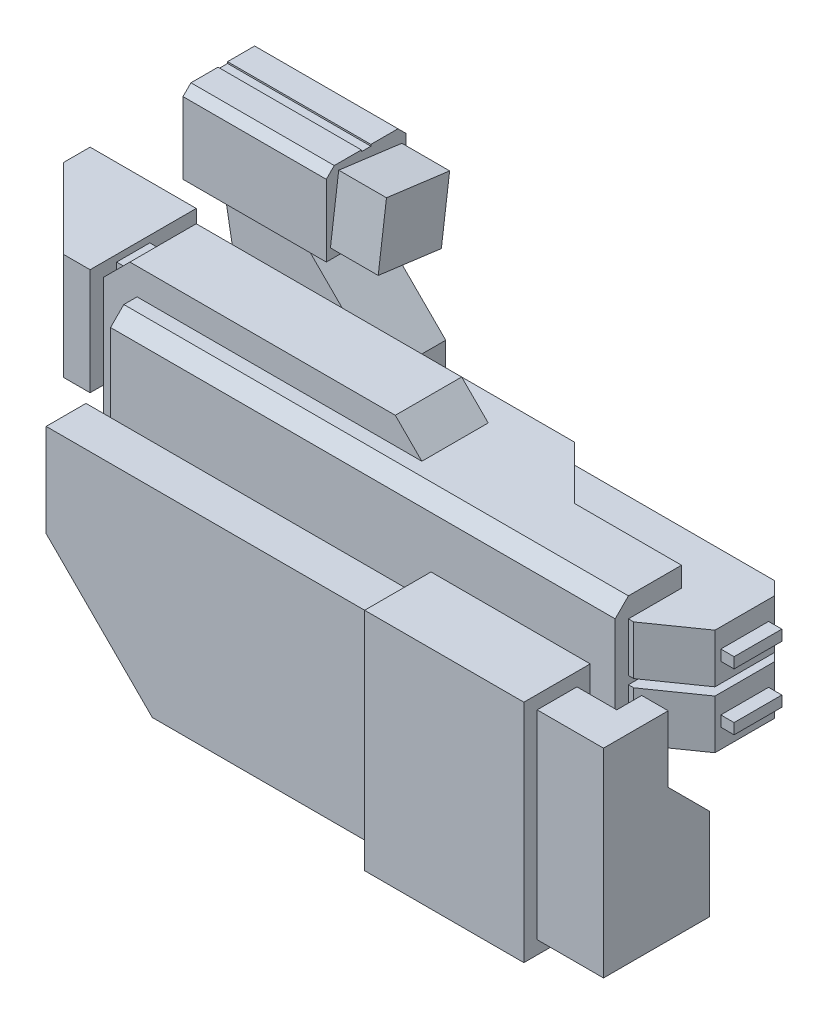
SolidWorks part; units mm, degrees
ref_plane "Front Plane" through (0, 0, 0) normal (0, 0, 1) x (1, 0, 0)
ref_plane "Top Plane" through (0, 0, 0) normal (0, 1, 0) x (1, 0, 0)
ref_plane "Right Plane" through (0, 0, 0) normal (1, 0, 0) x (0, 0, -1)
sketch "Sketch1" plane through (0, 0, 0) normal (0, 0, 1) x (1, 0, 0)
  line L0 (0, 0) -> (0, 25.4)
  line L1 (0, 25.4) -> (12.7, 25.4)
  line L2 (12.7, 25.4) -> (25.4, 12.7)
  line L3 (25.4, 12.7) -> (25.4, 0)
  line L5 (25.4, 0) -> (25.4, -12.7)
  line L6 (25.4, -12.7) -> (0, -12.7)
  line L7 (0, -12.7) -> (0, 0)
extrude "Boss-Extrude1" add sketch "Sketch1" along normal blind 10.16
ref_plane "Plane1" through (0, 0, 0) normal (-1, 0, 0) x (0, 0, 1)
sketch "Sketch2" plane through (0, 0, 0) normal (-1, 0, 0) x (0, 0, 1)
  line L0 (5.08, 25.4) -> (11.43, 25.4)
  line L1 (10.16, 25.4) -> (0, 25.4) construction
  line L2 (11.43, 25.4) -> (11.43, 38.1)
  line L3 (11.43, 38.1) -> (-1.27, 38.1)
  line L4 (-1.27, 38.1) -> (-1.27, 25.4)
  line L5 (-1.27, 25.4) -> (5.08, 25.4)
extrude "Boss-Extrude2" add sketch "Sketch2" against normal blind 17.78 and the other way blind 5.08
chamfer "Chamfer1" distance 1.27 angle 45 2 edges at (6.35, 38.1, -1.27) (6.35, 38.1, 11.43)
sketch "Sketch3" plane through (17.78, 0, 0) normal (1, 0, 0) x (0, 0, -1)
  line L0 (-11.43, 25.4) -> (1.27, 25.4)
  line L1 (-5.08, 25.4) -> (-5.08, 31.75)
  line L2 (-10.7723, 27.0277) -> (-9.451, 37.1014)
  line L3 (-9.451, 37.1014) -> (0.6227, 35.7802)
  line L4 (0.6227, 35.7802) -> (-0.6986, 25.7064)
  line L5 (-0.6986, 25.7064) -> (-10.7723, 27.0277)
extrude "Boss-Extrude3" add sketch "Sketch3" along normal blind 7.62 contours L5 L4 L3 L2 region at (17.78, 31.4039, 5.0748)
sketch "Sketch4" plane through (0, 38.1, 0) normal (0, 1, 0) x (1, 0, 0)
  line L0 (17.78, -10.16) -> (17.78, 0)
  line L2 (-5.08, -10.16) -> (-5.08, 0) construction
  line L3 (-5.08, -5.08) -> (-5.08, -4.318)
  line L4 (-5.08, -4.318) -> (17.78, -4.318)
  line L5 (17.78, -4.318) -> (17.78, -5.842)
  line L6 (17.78, -5.842) -> (-5.08, -5.842)
  line L7 (-5.08, -5.842) -> (-5.08, -4.318)
  line M7 (-5.08, 0) -> (-5.08, -10.16)
extrude "Cut-Extrude1" cut sketch "Sketch4" against normal blind 0.254 contours L6 L0 L4 M7 region at (6.35, 38.1, 5.08)
scale "Scale1" scale about centroid uniform scaling yes scale factor 0.6
sketch "Sketch6" plane through (0, 0, 2.0319) normal (0, 0, -1) x (-1, 0, 0)
  line L0 (-19.6335, 13.1296) -> (-4.3935, -2.1104)
  line L1 (-12.0135, 5.5096) -> (-12.0135, 10.5896)
  line L7 (-15.8235, 9.3196) -> (-8.2035, 1.6996) construction
  line L8 (-15.8235, 14.3996) -> (-8.2035, 14.3996)
  line L9 (-15.8235, 14.3996) -> (-15.8235, 6.7796)
  line L10 (-15.8235, 6.7796) -> (-8.2035, 6.7796)
  line L11 (-8.2035, 14.3996) -> (-8.2035, 6.7796)
  line L12 (-15.8235, 14.3996) -> (-8.2035, 6.7796) construction
  line L13 (-15.8235, 6.7796) -> (-8.2035, 14.3996) construction
  point P4 (-12.0135, 5.5096)
  dimension "D1" = 7.62
  dimension "D2" = 7.62
chamfer "Chamfer3" distance 24.13 angle 10 1 edges at (4.3935, -2.1104, 5.0799) first distance on face at (4.3935, 9.3196, 5.0799)
sketch "Sketch8" plane through (0, 0, 8.1279) normal (0, 0, 1) x (1, 0, 0)
  line L0 (19.6335, -2.1104) -> (29.7935, -2.1104)
  line L1 (29.7935, -2.1104) -> (29.7935, 16.9396)
  line L2 (29.7935, 16.9396) -> (-0.6865, 16.9396)
  line L3 (-0.6865, 16.9396) -> (-0.6865, -2.1104)
  line L4 (-0.6865, -2.1104) -> (19.6335, -2.1104)
extrude "Boss-Extrude7" add sketch "Sketch8" along normal blind 6.35
chamfer "Chamfer4" distance 2.54 angle 45 4 edges at (29.7935, 16.9396, 11.3029) (29.7935, -2.1104, 11.3029) (-0.6865, -2.1104, 11.3029) (-0.6865, 16.9396, 11.3029)
sketch "Sketch9" plane through (0, -2.1104, 0) normal (0, -1, 0) x (1, 0, 0)
  line L0 (1.8535, 8.1279) -> (8.6483, 8.1279) construction
  line L1 (19.6335, 2.0319) -> (8.6483, 2.0319)
  line L2 (19.6335, 2.0319) -> (19.6335, 8.1279)
  line L3 (19.6335, 8.1279) -> (8.6483, 8.1279)
  line L4 (8.6483, 2.0319) -> (8.6483, 8.1279)
  line L5 (8.6483, 2.0319) -> (4.3931, 2.0319)
  line L6 (8.6483, 2.0319) -> (8.6483, 8.1279)
  line L7 (8.6483, 8.1279) -> (4.3931, 8.1279)
  line L8 (4.3931, 2.0319) -> (4.3931, 8.1279)
  line M9 (1.8535, 8.1279) -> (8.6483, 8.1279)
  line M10 (8.6483, 8.1279) -> (8.6483, 2.0319)
  line M11 (8.6483, 2.0319) -> (19.6335, 2.0319)
  line M12 (19.6335, 2.0319) -> (19.6335, 8.1279)
extrude "Cut-Extrude4" cut sketch "Sketch9" against normal blind 1.27 contours L3 M12 M10 M11 | L8 L5 M10 M9 region at (14.1409, -2.1104, 5.0799) region at (6.5207, -2.1104, 5.0799)
sketch "Sketch10" plane through (0, 0, 0) normal (-1, 0, 0) x (0, 0, 1)
  line L0 (14.4779, 14.3996) -> (14.4779, 0.4296)
  line L1 (14.4779, 0.4296) -> (17.0179, 0.4296)
  line L2 (17.0179, 0.4296) -> (17.0179, 14.3996)
  line L3 (17.0179, 14.3996) -> (14.8611, 14.3996)
  line L4 (14.4779, 14.3996) -> (14.8611, 14.3996)
extrude "Boss-Extrude8" add sketch "Sketch10" against normal blind 63.5
sketch "Sketch12" plane through (0, 0, 0) normal (-1, 0, 0) x (0, 0, 1)
  line L0 (17.0179, 14.3996) -> (14.4779, 14.3996) construction
  line L1 (14.6198, 14.3996) -> (17.0179, 14.3996)
  line L2 (14.6198, 14.3996) -> (14.6198, 0.4296)
  line L3 (14.6198, 0.4296) -> (17.0179, 0.4296)
  line L4 (17.0179, 14.3996) -> (17.0179, 0.4296)
  line L6 (14.6198, 14.3996) -> (14.4779, 14.3996)
  line L7 (14.6198, 14.3996) -> (14.6198, 0.4296)
  line L8 (14.6198, 0.4296) -> (14.4779, 0.4296)
  line L9 (14.4779, 14.3996) -> (14.4779, 0.4296)
  line M5 (17.0179, 14.3996) -> (14.4779, 14.3996)
  line M6 (14.4779, 14.3996) -> (14.4779, 0.4296)
  line M7 (14.4779, 0.4296) -> (17.0179, 0.4296)
  line M8 (17.0179, 0.4296) -> (17.0179, 14.3996)
extrude "Cut-Extrude7" cut sketch "Sketch12" against normal blind 2.54 contours L2 M5 M6 M7 | L2 M5 M7 M8 region at (0, 7.4146, 15.8188) region at (0, 7.4146, 14.5488)
chamfer "Chamfer5" distance 1.27 angle 45 2 edges at (33.02, 0.4296, 17.0179) (33.02, 14.3996, 17.0179)
sketch "Sketch14" plane through (-0.6865, 0, 0) normal (-1, 0, 0) x (0, 0, 1)
  line L1 (8.1279, 14.3996) -> (11.9379, 14.3996)
  line L2 (8.1279, 14.3996) -> (8.1279, 6.7796)
  line L3 (8.1279, 6.7796) -> (11.9379, 6.7796)
  line L4 (11.9379, 14.3996) -> (11.9379, 6.7796)
  dimension "D1" = 7.62
  dimension "D2" = 3.81
extrude "Boss-Extrude9" add sketch "Sketch14" along normal blind 1.27
sketch "Sketch15" plane through (-1.9565, 0, 0) normal (-1, 0, 0) x (0, 0, 1)
  line L0 (11.9379, 6.7796) -> (11.9379, 4.2007)
  line L1 (11.9379, 4.2007) -> (14.4779, 4.2007)
  line L2 (11.9379, 14.3996) -> (14.4779, 14.3996)
  line L3 (11.9379, 14.3996) -> (4.3179, 14.3996)
  line L4 (11.9379, 14.3996) -> (8.1279, 14.3996) construction
  line L6 (4.3179, 14.3996) -> (14.4779, 14.3996)
  line L7 (4.3179, 14.3996) -> (4.3179, 4.2007)
  line L8 (4.3179, 4.2007) -> (14.4779, 4.2007)
  line L9 (14.4779, 14.3996) -> (14.4779, 4.2007)
  point P8 (14.4779, 14.3996)
  line M1 (8.1279, 14.3996) -> (8.1279, 6.7796)
  line M2 (8.1279, 6.7796) -> (11.9379, 6.7796)
  line M3 (11.9379, 6.7796) -> (11.9379, 14.3996)
  line M4 (11.9379, 14.3996) -> (8.1279, 14.3996)
extrude "Boss-Extrude10" add sketch "Sketch15" along normal blind 10.16 contours L7 L8 L0 L3 M2 M1 | M4 M1 M2 M3 | L9 L2 L0 L1 M3 region at (-1.9565, 9.3001, 13.2079) region at (-1.9565, 8.5312, 6.9918) region at (-1.9565, 10.5896, 10.0329)
sketch "Sketch16" plane through (0, 0, 8.1279) normal (0, 0, -1) x (-1, 0, 0)
  line L1 (0.6865, 14.3996) -> (1.9565, 14.3996)
  line L2 (0.6865, 14.3996) -> (0.6865, 6.7796)
  line L3 (0.6865, 6.7796) -> (1.9565, 6.7796)
  line L4 (1.9565, 14.3996) -> (1.9565, 6.7796)
extrude "Cut-Extrude8" cut sketch "Sketch16" against normal blind 0.635
sketch "Sketch17" plane through (0, 14.3996, 0) normal (0, 1, 0) x (1, 0, 0)
  line L1 (-0.6865, -11.9379) -> (-1.9565, -11.9379)
  line L2 (-0.6865, -11.9379) -> (-0.6865, -8.7629)
  line L3 (-0.6865, -8.7629) -> (-1.9565, -8.7629)
  line L4 (-1.9565, -11.9379) -> (-1.9565, -8.7629)
extrude "Cut-Extrude9" cut sketch "Sketch17" against normal blind 0.635
chamfer "Chamfer6" distance 7.62 angle 45 1 edges at (-12.1165, 9.3001, 14.4779)
sketch "Sketch18" plane through (0, 0, 8.1279) normal (0, 0, -1) x (-1, 0, 0)
  line L0 (-27.2535, -2.1104) -> (-29.7935, 0.4296)
  line L1 (-29.7935, 0.4296) -> (-29.7935, -2.1104)
  line L2 (-29.7935, -2.1104) -> (-27.2535, -2.1104)
extrude "Boss-Extrude11" add sketch "Sketch18" against normal blind 6.35
sketch "Sketch19" plane through (0, 0, 14.4779) normal (0, 0, -1) x (-1, 0, 0)
  line L0 (-63.5, 14.3996) -> (-63.5, 0.4296)
  line L1 (-63.5, 14.3996) -> (-29.7935, 14.3996) construction
  line L2 (-63.5, 14.3996) -> (-63.5, 0.4296) construction
  line L3 (-63.5, 0.4296) -> (-19.6335, 0.4296)
  line L4 (-19.6335, -0.8404) -> (-19.6335, 13.1296) construction
  line L5 (-19.6335, 0.4296) -> (-19.6335, 14.3996)
  line L6 (-19.6335, 14.3996) -> (-63.5, 14.3996)
extrude "Boss-Extrude12" add sketch "Sketch19" along normal blind 10.16
chamfer "Chamfer7" distance 1.27 angle 45 2 edges at (41.5668, 0.4296, 4.3179) (41.5668, 14.3996, 4.3179)
sketch "Sketch20" plane through (0, 14.3996, 0) normal (0, 1, 0) x (1, 0, 0)
  line L1 (41.8574, -1.7365) -> (63.5, -1.7365)
  line L2 (50.8344, -10.6679) -> (50.8344, -4.3501)
  line L3 (50.8344, -4.3501) -> (44.4844, -4.3501)
  line L4 (44.4844, -4.3501) -> (50.8344, -10.6679)
  line L5 (63.5, -15.7479) -> (63.5, -5.5879) construction
  line L6 (50.8344, -4.3501) -> (63.5, -4.3501)
  line L8 (50.8344, -4.3501) -> (50.8344, -10.6679)
  line L9 (50.8344, -10.6679) -> (63.5, -10.6679)
  line L14 (63.5, -4.3501) -> (63.5, -10.6679)
  line L15 (44.4844, -4.3501) -> (41.8574, -1.7365)
  line L16 (63.5, -1.7365) -> (63.5, -4.3501)
  line M1 (63.5, -15.7479) -> (63.5, -5.5879)
  line M2 (63.5, -5.5879) -> (19.6335, -5.5879)
extrude "Cut-Extrude12" cut sketch "Sketch20" against normal blind 17.78 contours L16 L1 L15 L3 L6 | L2 L9 M1 M2 | L3 L4 L2 M2 | L4 L2 M2 | L14 L6 L2 M2 region at (53.3213, 14.3996, 3.0152) region at (47.9591, 14.3996, 4.9466) region at (57.1672, 14.3996, 4.969) region at (49.1324, 14.3996, 7.2812) region at (57.1672, 14.3996, 8.1279)
extrude "Boss-Extrude13" add sketch "Sketch6" along normal blind 1.27 contours L11 L8 L9 L0 L10 | L9 L10 L0 region at (11.8392, 10.7639, 2.0319) region at (14.9769, 7.6262, 2.0319)
sketch "Sketch21" plane through (0, 14.3996, 0) normal (0, 1, 0) x (1, 0, 0)
  line L0 (50.8344, -10.6679) -> (50.8344, -17.0179)
  line L1 (50.8344, -17.0179) -> (63.5, -17.0179)
  line L2 (63.5, -17.0179) -> (63.5, -10.6679)
  line L3 (63.5, -10.6679) -> (50.8344, -10.6679)
extrude "Cut-Extrude14" cut sketch "Sketch21" against normal blind 17.78
sketch "Sketch22" plane through (0, 14.3996, 0) normal (0, 1, 0) x (1, 0, 0)
  line L0 (50.8344, -10.6679) -> (40.605, -10.6679)
  line L1 (40.605, -10.6679) -> (33.0662, -3.1291)
  line L2 (33.0662, -3.1291) -> (50.8344, -3.4641)
  line L3 (50.8344, -3.4641) -> (50.8344, -10.6679)
extrude "Cut-Extrude15" cut sketch "Sketch22" against normal blind 17.78
ref_plane "Plane2" through (53.3744, 0, 0) normal (1, 0, 0) x (0, 0, -1)
sketch "Sketch24" plane through (53.3744, 0, 0) normal (1, 0, 0) x (0, 0, -1)
  line L0 (-15.7479, 0.4296) -> (-13.0538, -2.2645)
  line L1 (-13.0538, -2.2645) -> (-13.0538, -11.0004)
  line L2 (-13.0538, -11.0004) -> (-23.2138, -11.0004)
  line L3 (-23.2138, -11.0004) -> (-23.2138, 8.0496)
  line L4 (-23.2138, 8.0496) -> (-17.0179, 8.0496)
  line L5 (-17.0179, 1.6996) -> (-17.0179, 13.1296) construction
  line L6 (-17.0179, 8.0496) -> (-17.0179, 1.6996)
  line L7 (-17.0179, 1.6996) -> (-15.7479, 0.4296)
  dimension "D1" = 6.35
extrude "Boss-Extrude14" add sketch "Sketch24" along normal blind 2.54 separate body
sketch "Sketch25" plane through (53.3744, 0, 0) normal (-1, 0, 0) x (0, 0, 1)
  line L0 (17.0179, 8.0496) -> (23.2138, 8.0496) construction
  line L1 (23.2138, -11.0004) -> (19.4038, -11.0004)
  line L2 (23.2138, -11.0004) -> (23.2138, 8.0496)
  line L3 (23.2138, 8.0496) -> (19.4038, 8.0496)
  line L4 (19.4038, -11.0004) -> (19.4038, 8.0496)
  dimension "D1" = 3.81
extrude "Boss-Extrude15" add sketch "Sketch25" along normal blind 50.8
chamfer "Chamfer8" distance 10.16 angle 45 1 edges at (2.5744, -11.0004, 21.3088)
sketch "Sketch26" plane through (0, 0, 17.0179) normal (0, 0, 1) x (1, 0, 0)
  line L5 (2.54, 1.6996) -> (5.08, 1.6996)
  line L6 (2.54, 1.6996) -> (50.8344, 1.6996) construction
  line L7 (50.8344, 1.6996) -> (50.8344, 13.1296) construction
  line L8 (5.08, 1.6996) -> (50.8344, 1.6996)
  line L9 (5.08, 1.6996) -> (5.08, 5.5802)
  line L10 (5.08, 5.5802) -> (50.8344, 5.5802)
  line L11 (50.8344, 1.6996) -> (50.8344, 5.5802)
extrude "Boss-Extrude18" add sketch "Sketch26" along normal blind 5.08 contours L9 L10 L11 L8
sketch "Sketch27" plane through (0, 0, 23.2138) normal (0, 0, 1) x (1, 0, 0)
  line L0 (55.9144, -11.0004) -> (49.5644, -11.0004)
  line L1 (55.9144, -11.0004) -> (12.7344, -11.0004) construction
  line L2 (49.5644, -11.0004) -> (49.5644, -12.2704)
  line L3 (49.5644, -12.2704) -> (34.3244, -12.2704)
  line L4 (34.3244, -12.2704) -> (34.3244, 8.0496)
  line L5 (55.9144, 8.0496) -> (2.5744, 8.0496) construction
  line L6 (34.3244, 8.0496) -> (34.3244, 9.3196)
  line L7 (34.3244, 9.3196) -> (49.5644, 9.3196)
  line L8 (49.5644, 9.3196) -> (49.5644, -11.0004)
  line M3 (12.7344, -11.0004) -> (55.9144, -11.0004)
  line M5 (55.9144, 8.0496) -> (2.5744, 8.0496)
extrude "Boss-Extrude19" add sketch "Sketch27" along normal blind 1.27 and the other way blind 5.08 contours L8 L4 M5 M3 | L8 L7 L6 M5 | L4 L3 L2 M3 region at (41.9444, -1.4754, 23.2138) region at (41.9444, -11.6354, 23.2138) region at (41.9444, 8.6846, 23.2138)
sketch "Sketch28" plane through (0, -2.1104, 0) normal (0, -1, 0) x (1, 0, 0)
  line L0 (1.8535, 11.3029) -> (29.7935, 11.3029)
  line L1 (1.8535, 14.4779) -> (1.8535, 8.1279) construction
  line L2 (29.7935, 14.4779) -> (29.7935, 8.1279) construction
  line L4 (20.9035, 10.0329) -> (10.7435, 10.0329)
  line L5 (20.9035, 10.0329) -> (20.9035, 12.5729)
  line L6 (20.9035, 12.5729) -> (10.7435, 12.5729)
  line L7 (10.7435, 10.0329) -> (10.7435, 12.5729)
  line L8 (20.9035, 10.0329) -> (10.7435, 12.5729) construction
  line L9 (20.9035, 12.5729) -> (10.7435, 10.0329) construction
  point P6 (15.8235, 11.3029)
  dimension "D1" = 2.54
  dimension "D2" = 10.16
extrude "Boss-Extrude20" add sketch "Sketch28" along normal blind 2.54 contours L7 L0 L5 L6 | L7 L4 L5 L0 region at (15.8235, -2.1104, 11.9379) region at (15.8235, -2.1104, 10.6679)
ref_plane "Plane3" through (0, -4.6504, 0) normal (0, -1, 0) x (-1, 0, 0)
sketch "Sketch29" plane through (0, -4.6504, 0) normal (0, -1, 0) x (-1, 0, 0)
  line L0 (-10.7435, -10.0329) -> (-5.6635, -10.0329)
  line L1 (-5.6635, -10.0329) -> (-5.6635, -7.4929)
  line L2 (-20.9035, -12.5729) -> (-25.9835, -12.5729)
  line L3 (-25.9835, -12.5729) -> (-25.9835, -15.1129)
  line L5 (-25.9835, -15.1129) -> (-5.6635, -15.1129)
  line L6 (-25.9835, -15.1129) -> (-25.9835, -7.4929)
  line L7 (-25.9835, -7.4929) -> (-5.6635, -7.4929)
  line L8 (-5.6635, -15.1129) -> (-5.6635, -7.4929)
extrude "Boss-Extrude21" add sketch "Sketch29" along normal blind 7.62 contours L5 L8 L1 L7 L6 L3 region at (15.8235, -4.6504, 11.3029)
chamfer "Chamfer9" distance 5.08 angle 45 1 edges at (25.9835, -12.2704, 11.3029)
sketch "Sketch30" plane through (5.6635, 0, 0) normal (-1, 0, 0) x (0, 0, 1)
  line L0 (7.4929, -12.2704) -> (7.4929, -13.0324)
  line L1 (7.4929, -13.0324) -> (6.7309, -13.0324)
  line L2 (15.1129, -4.6504) -> (15.1129, -3.8884)
  line L3 (15.1129, -3.8884) -> (15.8749, -3.8884)
  line L5 (15.8749, -3.8884) -> (6.7309, -3.8884)
  line L6 (15.8749, -3.8884) -> (15.8749, -13.0324)
  line L7 (15.8749, -13.0324) -> (6.7309, -13.0324)
  line L8 (6.7309, -3.8884) -> (6.7309, -13.0324)
  line M1 (15.1129, -4.6504) -> (7.4929, -4.6504)
  line M2 (7.4929, -4.6504) -> (7.4929, -12.2704)
  line M3 (7.4929, -12.2704) -> (15.1129, -12.2704)
  line M4 (15.1129, -12.2704) -> (15.1129, -4.6504)
extrude "Boss-Extrude22" add sketch "Sketch30" along normal blind 3.81 contours L5 L8 L1 L0 L2 M2 M1 | L7 L6 L3 L2 L0 M4 M3 | M4 M1 M2 M3 region at (5.6635, -12.3945, 11.3029) region at (5.6635, -12.6514, 7.3688) region at (5.6635, -8.4604, 11.3029)
sketch "Sketch31" plane through (50.8344, 0, 0) normal (1, 0, 0) x (0, 0, -1)
  line L0 (-10.6679, 14.3996) -> (-10.6679, 0.4296)
  line L2 (-15.7479, 2.3346) -> (-5.5879, 2.3346)
  line L3 (-15.7479, 2.3346) -> (-15.7479, 12.4946)
  line L4 (-15.7479, 12.4946) -> (-5.5879, 12.4946)
  line L5 (-5.5879, 2.3346) -> (-5.5879, 12.4946)
  line L6 (-15.7479, 2.3346) -> (-5.5879, 12.4946) construction
  line L7 (-15.7479, 12.4946) -> (-5.5879, 2.3346) construction
  point P4 (-10.6679, 7.4146)
  dimension "D1" = 10.16
  dimension "D2" = 10.16
extrude "Boss-Extrude24" add sketch "Sketch31" along normal blind 5.08 and the other way blind 20.32 contours L2 L5 L4 L0 | L4 L3 L2 L0 region at (50.8344, 7.4146, 8.1279) region at (50.8344, 7.4146, 13.2079)
sketch "Sketch32" plane through (55.9144, 0, 0) normal (1, 0, 0) x (0, 0, -1)
  line L0 (-15.7479, 7.4146) -> (-5.5879, 7.4146)
  line L1 (-15.7479, 2.3346) -> (-15.7479, 12.4946) construction
  line L2 (-5.5879, 2.3346) -> (-5.5879, 12.4946) construction
  line L4 (-15.7479, 7.0336) -> (-5.5879, 7.0336)
  line L5 (-15.7479, 7.0336) -> (-15.7479, 7.7956)
  line L6 (-15.7479, 7.7956) -> (-5.5879, 7.7956)
  line L7 (-5.5879, 7.0336) -> (-5.5879, 7.7956)
  line L8 (-15.7479, 7.0336) -> (-5.5879, 7.7956) construction
  line L9 (-15.7479, 7.7956) -> (-5.5879, 7.0336) construction
  point P6 (-10.6679, 7.4146)
  dimension "D1" = 0.762
extrude "Cut-Extrude16" cut sketch "Sketch32" against normal blind 5.08 contours L6 L7 L4 L5
sketch "Sketch33" plane through (50.8344, 0, 0) normal (1, 0, 0) x (0, 0, -1)
  line L0 (-15.7479, 7.7956) -> (-5.5879, 7.7956) construction
  line L1 (-5.5879, 7.0336) -> (-10.6679, 7.0336)
  line L2 (-5.5879, 7.0336) -> (-5.5879, 7.7956)
  line L3 (-5.5879, 7.7956) -> (-10.6679, 7.7956)
  line L4 (-10.6679, 7.0336) -> (-10.6679, 7.7956)
extrude "Cut-Extrude17" cut sketch "Sketch33" against normal blind 15.24
chamfer "Chamfer10" distance 4.572 angle 35 1 edges at (55.9144, 4.6841, 15.7479) first distance on face at (53.3744, 4.6841, 15.7479)
chamfer "Chamfer11" distance 4.572 angle 35 1 edges at (55.9144, 10.1451, 15.7479) first distance on face at (53.3744, 10.1451, 15.7479)
chamfer "Chamfer12" distance 1.27 angle 45 1 edges at (55.9144, 4.6841, 5.5879)
sketch "Sketch35" plane through (55.9144, 0, 0) normal (1, 0, 0) x (0, 0, -1)
  line L0 (-12.5465, 12.4946) -> (-6.8579, 7.7956)
  line L1 (-12.5465, 12.4946) -> (-12.5465, 7.7956) construction
  line L2 (-12.5465, 7.0336) -> (-6.8579, 2.3346)
  line L3 (-6.8579, 2.3346) -> (-6.8579, 7.0336) construction
  line L4 (-12.5465, 2.3346) -> (-6.8579, 2.3346) construction
  line L6 (-11.9882, 9.6371) -> (-7.4162, 9.6371)
  line L7 (-11.9882, 9.6371) -> (-11.9882, 10.6531)
  line L8 (-11.9882, 10.6531) -> (-7.4162, 10.6531)
  line L9 (-7.4162, 9.6371) -> (-7.4162, 10.6531)
  line L10 (-11.9882, 9.6371) -> (-7.4162, 10.6531) construction
  line L11 (-11.9882, 10.6531) -> (-7.4162, 9.6371) construction
  line L12 (-11.9882, 4.1761) -> (-7.4162, 4.1761)
  line L13 (-11.9882, 4.1761) -> (-11.9882, 5.1921)
  line L14 (-11.9882, 5.1921) -> (-7.4162, 5.1921)
  line L15 (-7.4162, 4.1761) -> (-7.4162, 5.1921)
  line L16 (-11.9882, 4.1761) -> (-7.4162, 5.1921) construction
  line L17 (-11.9882, 5.1921) -> (-7.4162, 4.1761) construction
  point P12 (-9.7022, 10.1451)
  point P17 (-9.7022, 4.6841)
  dimension "D1" = 4.572
  dimension "D2" = 1.016
  dimension "D3" = 1.016
extrude "Boss-Extrude25" add sketch "Sketch35" along normal blind 1.27 contours L8 L7 L6 L0 | L6 L9 L8 L0 | L12 L15 L14 L2 | L14 L13 L12 L2 region at (55.9144, 10.1906, 8.5868) region at (55.9144, 10.0995, 10.8176) region at (55.9144, 4.7296, 8.5868) region at (55.9144, 4.6385, 10.8176)
